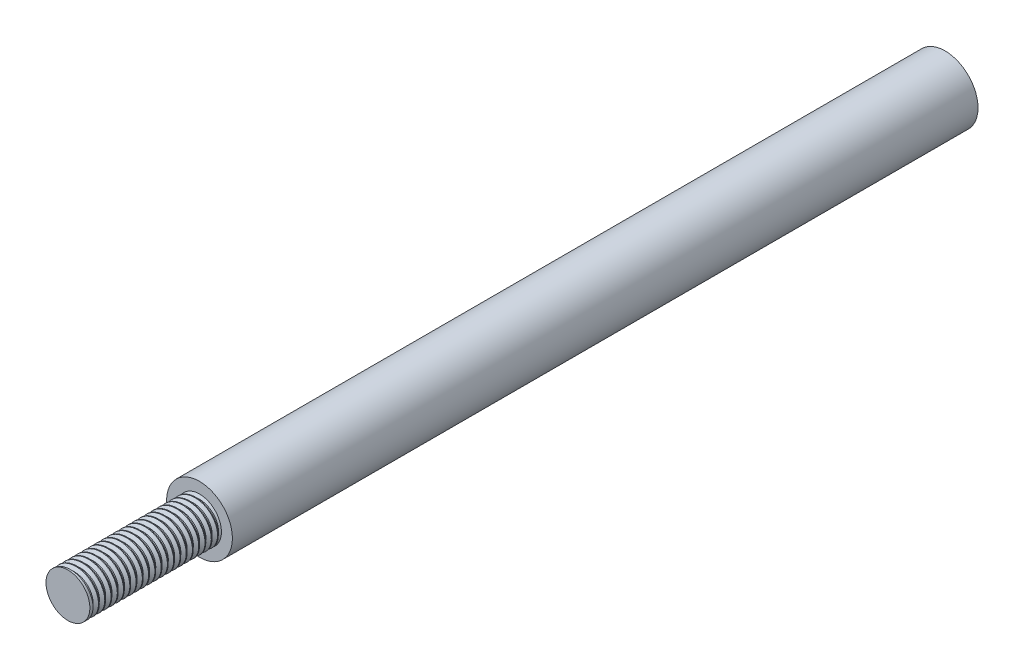
SolidWorks part; units mm, degrees
ref_plane "Front Plane" through (0, 0, 0) normal (0, 0, 1) x (1, 0, 0)
ref_plane "Top Plane" through (0, 0, 0) normal (0, 1, 0) x (1, 0, 0)
ref_plane "Right Plane" through (0, 0, 0) normal (1, 0, 0) x (0, 0, -1)
sketch "Sketch2" plane through (0, 0, 0) normal (0, 0, 1) x (1, 0, 0)
  circle A0 centre (0, 0) radius 4.7625
extrude "Boss-Extrude1" add sketch "Sketch2" along normal blind 107.95
sketch "Sketch3" plane through (0, 0, 107.95) normal (0, 0, 1) x (1, 0, 0)
  circle A0 centre (0, 0) radius 3.175
extrude "Boss-Extrude2" add sketch "Sketch3" along normal blind 19.05
thread "Thread1" pitch 0.9071 method cut profile "Thread Profile1" start angle 0, offset 0, length 0, pitch 0.9071, diameter 6.35
ref_plane "Plane1" through (-3.175, 0, 127) normal (0, -1, 0) x (-1, 0, 0)
sketch "Thread Profile1" plane through (-3.175, 0, 127) normal (0, -1, 0) x (-1, 0, 0)
  line L0 (0, 0) -> (0, 0.9071) construction
  line L11 (0, 0) -> (0, 0.7937)
  line L12 (0, 0.7937) -> (-0.491, 0.5103)
  line L13 (-0.491, 0.5103) -> (-0.491, 0.2835)
  line L15 (-0.491, 0.2835) -> (0, 0)
  line L17 (-0.491, 0.3969) -> (0, 0.3969) construction
  point P2 (0, 0)
  dimension "Pitch" = 0.9071
  dimension "Profile_Angle" = 60
  dimension "Profile_Land" = 0.2268
  dimension "Profile_Height" = 0.491
